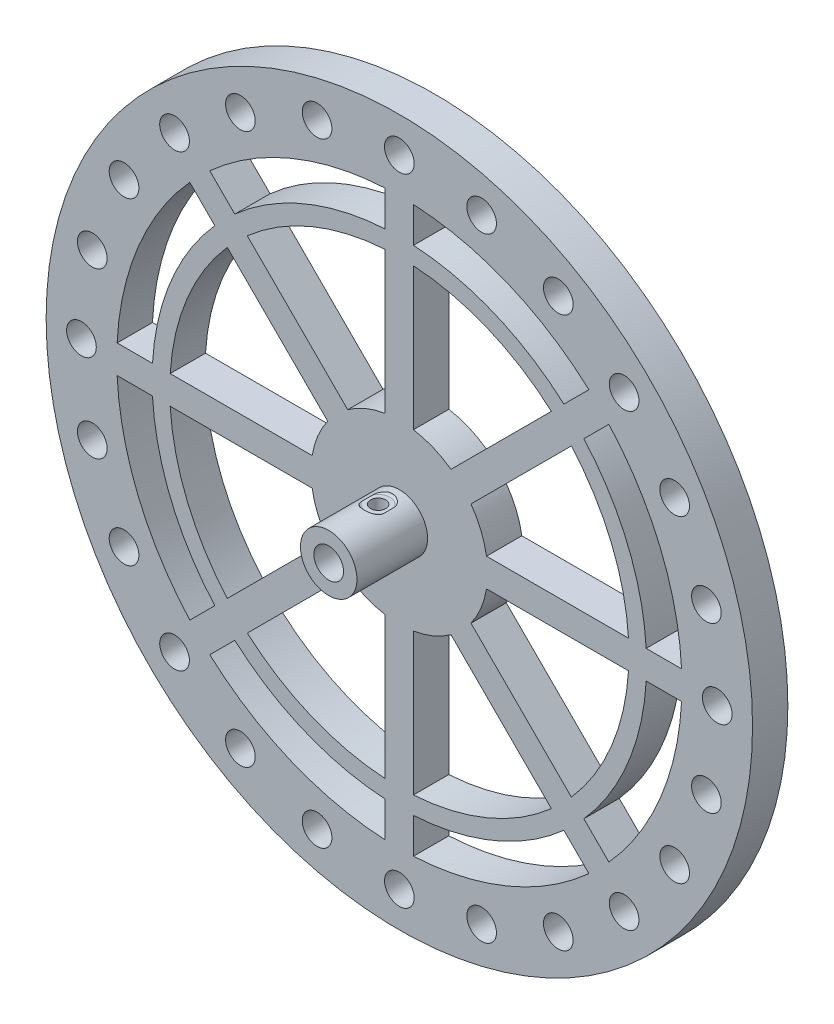
SolidWorks part; units mm, degrees
ref_plane "정면" through (0, 0, 0) normal (0, 0, 1) x (1, 0, 0)
ref_plane "윗면" through (0, 0, 0) normal (0, 1, 0) x (1, 0, 0)
ref_plane "우측면" through (0, 0, 0) normal (1, 0, 0) x (0, 0, -1)
sketch "Sketch1" plane through (0, 0, 0) normal (0, 0, 1) x (1, 0, 0)
  line L0 (-2, 39.95) -> (-2, 12.339)
  line L1 (2, 39.95) -> (2, 12.339)
  line L2 (0, 40) -> (0, 0) construction
  line L3 (26.8347, 29.6631) -> (7.3108, 10.1392)
  line L4 (29.6631, 26.8347) -> (10.1392, 7.3108)
  line L5 (39.95, 2) -> (12.339, 2)
  line L6 (39.95, -2) -> (12.339, -2)
  line L7 (29.6631, -26.8347) -> (10.1392, -7.3108)
  line L8 (26.8347, -29.6631) -> (7.3108, -10.1392)
  line L9 (2, -39.95) -> (2, -12.339)
  line L10 (-2, -39.95) -> (-2, -12.339)
  line L11 (-26.8347, -29.6631) -> (-7.3108, -10.1392)
  line L12 (-29.6631, -26.8347) -> (-10.1392, -7.3108)
  line L13 (-39.95, -2) -> (-12.339, -2)
  line L14 (-39.95, 2) -> (-12.339, 2)
  line L15 (-29.6631, 26.8347) -> (-10.1392, 7.3108)
  line L16 (-26.8347, 29.6631) -> (-7.3108, 10.1392)
  circle A0 centre (0, 0) radius 50
  circle A1 centre (0, 0) radius 40
  circle A2 centre (0, 0) radius 35
  circle A3 centre (0, 0) radius 32.5
  circle A4 centre (0, 0) radius 12.5
  point P28 (0, 0)
  dimension "D1" = 100
  dimension "D3" = 70
  dimension "D4" = 65
  dimension "D5" = 25
  dimension "D6" = 4
  dimension "D7" = 2
  dimension "D2" = 10
  dimension "D8" = 8
extrude "Extrude2" add sketch "Sketch1" along normal mid plane 5 contours A4 | A0 A1 | L2 A1 L0 A2 | A1 L2 A2 L1 | A2 L2 A3 L1 | L2 A2 L0 A3 | L2 A3 L0 A4 | A3 L2 A4 L1 | A4 L4 A3 L3 | A3 L4 A2 L3 | A2 L4 A1 L3 | A4 L6 A3 L5 | A3 L6 A2 L5 | A2 L6 A1 L5 | A4 L8 A3 L7 | A2 L8 A1 L7 | A3 L8 A2 L7 | A4 L10 A3 L9 | A3 L10 A2 L9 | A2 L10 A1 L9 | A4 L12 A3 L11 | A3 L12 A2 L11 | A2 L12 A1 L11 | A4 L14 A3 L13 | A3 L14 A2 L13 | A2 L14 A1 L13 | A4 L16 A3 L15 | A2 L16 A1 L15 | A3 L16 A2 L15 | A3 L0 A2 L16 | A3 L3 A2 L1 | A3 L5 A2 L4 | A3 L7 A2 L6 | A3 L9 A2 L8 | A3 L11 A2 L10 | A3 L13 A2 L12 | A3 L15 A2 L14 region at (-1.0002, 37.4821, 0) region at (-1.0003, 33.7302, 0) region at (-12.6844, 30.6228, 0) region at (1.0002, 37.4821, 0) region at (-26.5039, 26.5039, 0) region at (-1.0008, 22.4629, 0) region at (1.0003, 33.7302, 0) region at (-23.8509, 23.8509, 0) region at (-0.9749, 12.1073, 0) region at (1.0008, 22.4629, 0) region at (-15.8837, 15.8837, 0) region at (12.6844, 30.6228, 0) region at (-30.6228, 12.6844, 0) region at (26.5039, 26.5039, 0) region at (-37.4821, 0, 0) region at (23.8509, 23.8509, 0) region at (-33.7302, 0, 0) region at (15.8837, 15.8837, 0) region at (-22.4629, 0, 0) region at (30.6228, 12.6844, 0) region at (-30.6228, -12.6844, 0) region at (37.4821, 0, 0) region at (-26.5039, -26.5039, 0) region at (33.7302, 0, 0) region at (-23.8509, -23.8509, 0) region at (22.4629, 0, 0) region at (-15.8837, -15.8837, 0) region at (-12.6844, -30.6228, 0) region at (0, -37.4821, 0) region at (30.6228, -12.6844, 0) region at (0, -33.7302, 0) region at (26.5039, -26.5039, 0) region at (0, -22.4629, 0) region at (23.8509, -23.8509, 0) region at (12.6844, -30.6228, 0) region at (15.8837, -15.8837, 0) region at (-48.5858, 0, 0)
sketch "Sketch2" plane through (0, 0, 2.5) normal (0, 0, 1) x (1, 0, 0)
  circle A0 centre (0, 45) radius 2.1
  circle A1 centre (11.6469, 43.4667) radius 2.1
  circle A2 centre (22.5, 38.9711) radius 2.1
  circle A3 centre (31.8198, 31.8198) radius 2.1
  circle A4 centre (38.9711, 22.5) radius 2.1
  circle A5 centre (43.4667, 11.6469) radius 2.1
  circle A6 centre (45, 0) radius 2.1
  circle A7 centre (43.4667, -11.6469) radius 2.1
  circle A8 centre (38.9711, -22.5) radius 2.1
  circle A9 centre (31.8198, -31.8198) radius 2.1
  circle A10 centre (22.5, -38.9711) radius 2.1
  circle A11 centre (11.6469, -43.4667) radius 2.1
  circle A12 centre (0, -45) radius 2.1
  circle A13 centre (-11.6469, -43.4667) radius 2.1
  circle A14 centre (-22.5, -38.9711) radius 2.1
  circle A15 centre (-31.8198, -31.8198) radius 2.1
  circle A16 centre (-38.9711, -22.5) radius 2.1
  circle A17 centre (-43.4667, -11.6469) radius 2.1
  circle A18 centre (-45, 0) radius 2.1
  circle A19 centre (-43.4667, 11.6469) radius 2.1
  circle A20 centre (-38.9711, 22.5) radius 2.1
  circle A21 centre (-31.8198, 31.8198) radius 2.1
  circle A22 centre (-22.5, 38.9711) radius 2.1
  circle A23 centre (-11.6469, 43.4667) radius 2.1
  point P43 (0, 0)
  dimension "D2" = 4.2
  dimension "D1" = 45
  dimension "D3" = 24
extrude "Extrude3" cut sketch "Sketch2" against normal through all both and the other way through all
sketch "Sketch3" plane through (0, 0, 2.5) normal (0, 0, 1) x (1, 0, 0)
  circle A0 centre (0, 0) radius 4
  dimension "D1" = 8
extrude "Extrude4" add sketch "Sketch3" along normal blind 10
sketch "Sketch4" plane through (0, 0, 12.5) normal (0, 0, 1) x (1, 0, 0)
  circle A0 centre (0, 0) radius 2.1
  dimension "D1" = 4.2
extrude "Extrude5" cut sketch "Sketch4" against normal up to next
ref_plane "Plane1" through (0, 4, 0) normal (0, 1, 0) x (1, 0, 0)
sketch "Sketch5" plane through (0, 4, 0) normal (0, 1, 0) x (1, 0, 0)
  line L0 (-4, -2.5) -> (4, -2.5) construction
  circle A0 centre (0, -5.5) radius 1.075
  dimension "D2" = 2.15
  dimension "D1" = 3
extrude "Extrude6" cut sketch "Sketch5" against normal up to next
sketch "Sketch6" plane through (0, 4, 0) normal (0, 1, 0) x (1, 0, 0)
  circle A0 centre (0, -5.5) radius 2
  dimension "D1" = 4
extrude "Extrude7" cut sketch "Sketch6" against normal blind 0.3
fillet "Fillet1" radius 0.3 2 edges at (0, 3.7, 3.5) (0, 3.7, 7.5)
mirror "Mirror2" about plane through (0, 0, 0) normal (0, 1, 0) of "Fillet1", "Extrude7", "Extrude6"
